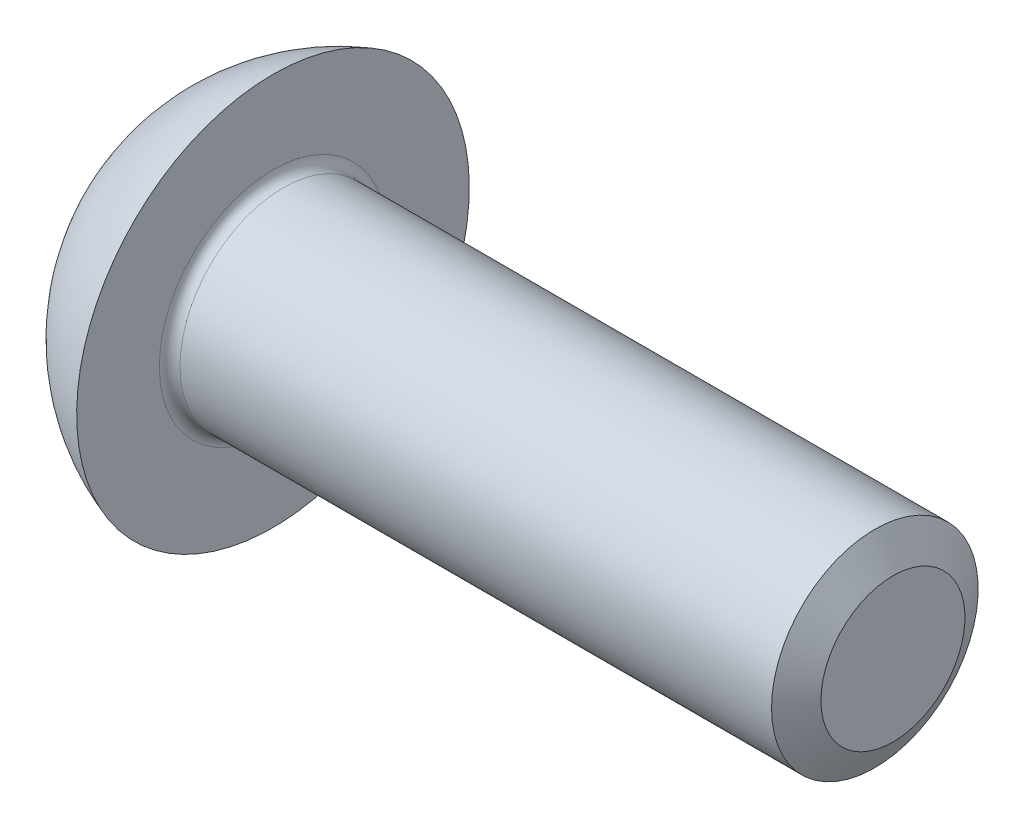
SolidWorks part; units mm, degrees
ref_plane "前视基准面" through (0, 0, 0) normal (0, 0, 1) x (1, 0, 0)
ref_plane "上视基准面" through (0, 0, 0) normal (0, 1, 0) x (1, 0, 0)
ref_plane "右视基准面" through (0, 0, 0) normal (1, 0, 0) x (0, 0, -1)
sketch "尺寸草图" plane through (0, 0, 0) normal (0, 0, 1) x (1, 0, 0)
  line L0 (0, 0) -> (12, 0) construction
  line L1 (12, 0) -> (12, 2) construction
  line L2 (12, 2) -> (11.3, 2) construction
  line L3 (0, 0) -> (0, 3.8) construction
  point P3 (1.4, 0)
  point P6 (12, 2.35)
  point P7 (0, 0.93)
  point P9 (2.2, 0)
  point P10 (2.4, 0)
  point P11 (12, 1.25)
  point P12 (3.7, 0)
  point P13 (4, 0)
  dimension "l" = 12
  dimension "d" = 4
  dimension "P" = 0.7
  dimension "a" = 1.4
  dimension "da" = 4.7
  dimension "dk" = 7.6
  dimension "e" = 2.87
  dimension "K" = 2.2
  dimension "r" = 0.2
  dimension "s" = 2.5
  dimension "t" = 1.3
  dimension "w" = 0.3
sketch "草图1" plane through (0, 0, 0) normal (0, 0, 1) x (1, 0, 0)
  line L0 (-14.2, 0) -> (0, 0) construction
  line L1 (0, 2) -> (-11.8, 2)
  line L2 (-12, 2.2) -> (-12, 3.8)
  line L3 (-14.2, 0) -> (-14.2, 2)
  line L4 (0, 2) -> (0, 0)
  line L5 (-14.2, 0) -> (0, 0)
  arc A0 (-12, 3.8) -> (-14.2, 2) centre (-10.7273, 0) ccw
  arc A1 (-11.8, 2) -> (-12, 2.2) centre (-11.8, 2.2) cw
  point P10 (-12, 2)
  dimension "r" = 0.2
  dimension "d" = 4
  dimension "dk" = 7.6
  dimension "k" = 2.2
  dimension "l" = 12
revolve "旋转1" add sketch "草图1" angle 360 about L0
cosmetic thread "装饰螺纹线1" parameters "D1"=10.6, "D2"=3.44
sketch "草图2" plane through (-14.2, 0, 0) normal (-1, 0, 0) x (0, 0, 1)
  line L1 (0, 1.4434) -> (-1.25, 0.7217)
  line L2 (-1.25, 0.7217) -> (-1.25, -0.7217)
  line L3 (-1.25, -0.7217) -> (0, -1.4434)
  line L4 (0, -1.4434) -> (1.25, -0.7217)
  line L5 (1.25, -0.7217) -> (1.25, 0.7217)
  line L6 (1.25, 0.7217) -> (0, 1.4434)
  circle A0 centre (0, 0) radius 1.25 construction
  dimension "s" = 2.5
extrude "切除-拉伸1" cut sketch "草图2" against normal blind 2.2
sketch "草图6" plane through (0, 0, 0) normal (0, 0, 1) x (1, 0, 0)
  line L0 (-12.9, 1.4434) -> (-12, 0)
  line L1 (-11.63, 1.4434) -> (-11.63, 0)
  line L2 (-11.63, 1.4434) -> (-12.9, 1.4434)
  line L3 (-14.2, 0) -> (-12, 0) construction
  line L4 (-11.63, 0) -> (-12, 0)
  line L5 (-14.2, 0) -> (-17.07, 0) construction
  dimension "t" = 1.3
  dimension "e-s" = 0.37
  dimension "k" = 2.2
  dimension "e" = 2.87
revolve "旋转2" add sketch "草图6" angle 360 about L3
sketch "草图7" plane through (0, 0, 0) normal (0, 0, 1) x (1, 0, 0)
  line L3 (-14.2, 1.4434) -> (-13.83, 0)
  line L4 (-14.2, 0) -> (-13.83, 0) construction
  line L7 (-14.2, 1.4434) -> (-14.2, 0)
  line L8 (-14.2, 0) -> (-13.83, 0)
  dimension "e-s" = 0.37
revolve "切除-旋转5" cut sketch "草图7" angle 360 about L4
sketch "草图4" plane through (0, 0, 0) normal (0, 0, 1) x (1, 0, 0)
  line L0 (-0.35, 2) -> (0, 1.3938)
  line L1 (-0.35, 2) -> (0.35, 2)
  line L2 (0.35, 2) -> (0, 1.3938)
  line L4 (0, -2) -> (0, 2) construction
  line L5 (-0.35, 0) -> (0.35, 0) construction
  dimension "d" = 2
  dimension "p" = 0.7
revolve "切除-旋转1" cut sketch "草图4" angle 360 about L5
ref_axis "基准轴1" through (-8.1887, 0, 0) along (1, 0, 0)
pattern_linear "阵列(线性)1" [suppressed] count 15 spacing 0.7 along (-1, 0, 0) of bodies 104
